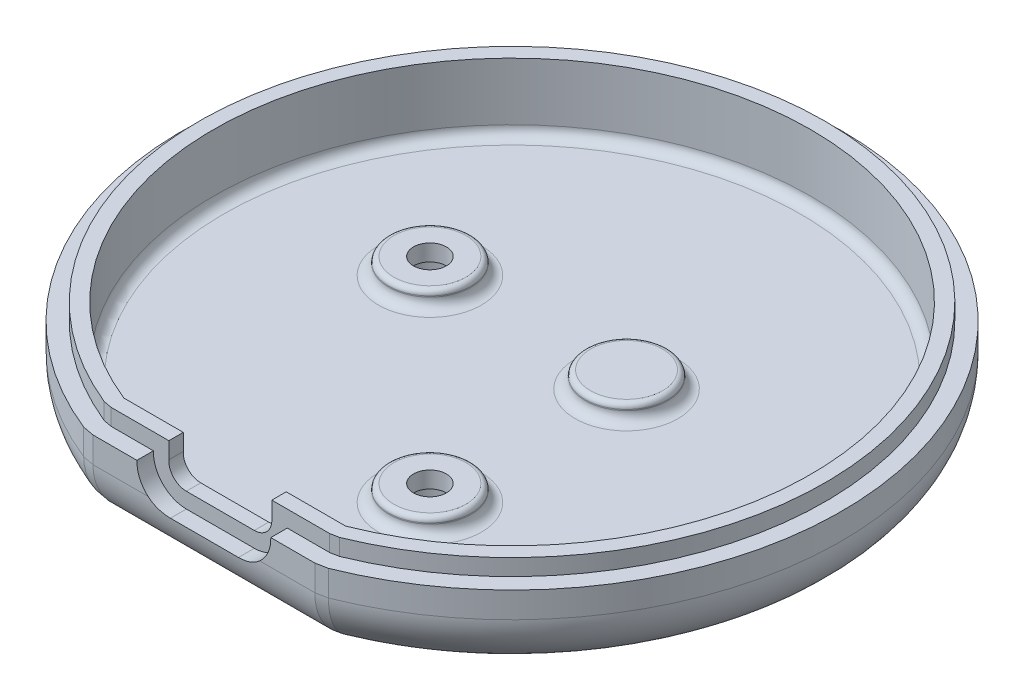
SolidWorks part; units mm, degrees
ref_plane "Front Plane" through (0, 0, 0) normal (0, 0, 1) x (1, 0, 0)
ref_plane "Top Plane" through (0, 0, 0) normal (0, 1, 0) x (1, 0, 0)
ref_plane "Right Plane" through (0, 0, 0) normal (1, 0, 0) x (0, 0, -1)
sketch "Sketch1" plane through (0, 0, 0) normal (0, 1, 0) x (1, 0, 0)
  line L0 (-10.7696, -29) -> (-11.8836, -28.7855)
  line L1 (25, -10.3553) -> (25, 10.3553)
  line L2 (25, 10.3553) -> (10.3553, 25)
  line L3 (10.3553, 25) -> (-10.3553, 25)
  line L4 (-10.3553, 25) -> (-25, 10.3553)
  line L5 (-25, 10.3553) -> (-25, -10.3553)
  line L6 (-25, -10.3553) -> (-10.3553, -25)
  line L7 (-10.3553, -25) -> (10.3553, -25)
  line L8 (10.3553, -25) -> (25, -10.3553)
  line L9 (10.7696, 26) -> (-10.7696, 26)
  line L10 (-10.7696, 26) -> (-26, 10.7696)
  line L11 (-26, 10.7696) -> (-26, -10.7696)
  line L12 (-26, -10.7696) -> (-10.7696, -26)
  line L13 (-10.7696, -26) -> (10.7696, -26)
  line L14 (10.7696, -26) -> (26, -10.7696)
  line L15 (26, -10.7696) -> (26, 10.7696)
  line L16 (26, 10.7696) -> (10.7696, 26)
  line L17 (-10.7696, -29) -> (10.7696, -29)
  line L18 (10.7696, -29) -> (11.8836, -28.7855)
  circle A0 centre (0, 0) radius 25 construction
  circle A1 centre (0, 0) radius 26 construction
  arc A2 (-10.7696, -26) -> (10.7696, -26) centre (0, 0.9261) cw
  arc A3 (-11.8836, -28.7855) -> (11.8836, -28.7855) centre (0, 0.9261) cw
  dimension "D3" = 29
  dimension "D1" = 50
  dimension "D2" = 1
  dimension "D4" = 3
  dimension "D5" = 3
extrude "Boss-Extrude1" add sketch "Sketch1" along normal blind 25 contours A3 L0 L17 L18 L13 A2 region at (-11.1582, 0, 28.0182)
sketch "Sketch2" plane through (0, 25, 0) normal (0, 1, 0) x (1, 0, 0)
  line L0 (10.7696, -29) -> (11.8836, -28.7855) construction
  line L1 (-10.7696, -29) -> (10.7696, -29) construction
  line L2 (-10.7696, -29) -> (-11.8836, -28.7855) construction
  line L3 (10.7696, -29) -> (11.8836, -28.7855)
  line L4 (-10.7696, -29) -> (10.7696, -29)
  line L5 (-10.7696, -29) -> (-11.8836, -28.7855)
  arc A0 (11.8836, -28.7855) -> (-11.8836, -28.7855) centre (0, 0.9261) ccw construction
  arc A1 (11.8836, -28.7855) -> (-11.8836, -28.7855) centre (0, 0.9261) ccw
extrude "Boss-Extrude2" add sketch "Sketch2" against normal blind 3
sketch "Sketch3" plane through (0, 0, 0) normal (0, -1, 0) x (1, 0, 0)
  line L0 (10.7696, 29) -> (11.8836, 28.7855) construction
  line L1 (-10.7696, 29) -> (10.7696, 29) construction
  line L2 (-10.7696, 29) -> (-11.8836, 28.7855) construction
  line L3 (10.7696, 29) -> (11.8836, 28.7855)
  line L4 (-10.7696, 29) -> (10.7696, 29)
  line L5 (-10.7696, 29) -> (-11.8836, 28.7855)
  arc A0 (-11.8836, 28.7855) -> (11.8836, 28.7855) centre (0, -0.9261) ccw construction
  arc A1 (-11.8836, 28.7855) -> (11.8836, 28.7855) centre (0, -0.9261) ccw
extrude "Boss-Extrude3" add sketch "Sketch3" against normal blind 3
sketch "Sketch5" plane through (0, 0, 29) normal (0, 0, 1) x (1, 0, 0)
  line L0 (0, 0) -> (0, 7.9) construction
  line L1 (-10.7696, 0) -> (10.7696, 0) construction
  line L2 (-3.3, 7.9) -> (3.3, 7.9) construction
  line L3 (-3.3, 9.6) -> (3.3, 9.6)
  line L4 (-3.3, 6.2) -> (3.3, 6.2)
  line L5 (-3.3, 11.1) -> (3.3, 11.1)
  line L6 (-3.3, 4.7) -> (3.3, 4.7)
  arc A0 (-3.3, 9.6) -> (-3.3, 6.2) centre (-3.3, 7.9) ccw
  arc A1 (3.3, 6.2) -> (3.3, 9.6) centre (3.3, 7.9) ccw
  arc A2 (3.3, 4.7) -> (3.3, 11.1) centre (3.3, 7.9) ccw
  arc A3 (-3.3, 11.1) -> (-3.3, 4.7) centre (-3.3, 7.9) ccw
  point P6 (0, 7.9)
  point P11 (-5, 7.9)
  point P12 (5, 7.9)
  dimension "D1" = 10
  dimension "D2" = 3.4
  dimension "D3" = 6.2
  dimension "D4" = 1.5
extrude "Cut-Extrude1" cut sketch "Sketch5" against normal blind 3 contours L4 A1 L3 A0 region at (0, 7.9, 29)
fillet "Fillet1" radius 5.5 4 edges at (0, 0, 29) (0, 0, -32.9261) (-11.3266, 0, 28.8927) (11.3266, 0, 28.8927)
fillet "Fillet2" radius 2 4 edges at (-11.3266, 25, 28.8927) (0, 25, -32.9261) (0, 25, 29) (11.3266, 25, 28.8927)
sketch "Sketch6" plane through (0, 3, 0) normal (0, 1, 0) x (1, 0, 0)
  line L0 (6.27, -13.32) -> (-12.8219, -13.32) construction
  line L1 (-12.8219, -13.32) -> (-12.8219, 5.7719) construction
  line L2 (10.7696, -26) -> (-10.7696, -26) construction
  line L3 (10.7696, -26) -> (-10.7696, -26)
  line L4 (6.27, -13.32) -> (6.27, 5.7719) construction
  line L5 (6.27, 5.7719) -> (-12.8219, 5.7719) construction
  circle A0 centre (-12.8219, 5.7719) radius 1.6
  circle A1 centre (6.27, -13.32) radius 1.6
  circle A2 centre (6.27, -13.32) radius 4
  circle A3 centre (-12.8219, 5.7719) radius 4
  circle A4 centre (6.27, 5.7719) radius 4
  point P9 (0, -26)
  dimension "D2" = 3.2
  dimension "D5" = 8
  dimension "D6" = 8
  dimension "D1" = 27
  dimension "D3" = 12.68
  dimension "D4" = 6.27
extrude "Boss-Extrude4" add sketch "Sketch6" along normal blind 1.6 contours A3 A0 | A4 | A2 A1 region at (2.3831, 3, 13.32) region at (-16.7087, 3, -5.7719) region at (6.27, 3, -5.7719)
fillet "Fillet3" radius 1 3 edges at (6.27, 3, 9.32) (6.27, 3, -9.7719) (-12.8219, 3, -9.7719)
fillet "Fillet4" radius 0.5 3 edges at (6.27, 4.6, 17.32) (6.27, 4.6, -1.7719) (-12.8219, 4.6, -1.7719)
sketch "Sketch7" plane through (0, 3, 0) normal (0, 1, 0) x (1, 0, 0)
  circle A0 centre (6.27, -13.32) radius 1.6 construction
  circle A1 centre (-12.8219, 5.7719) radius 1.6 construction
  circle A2 centre (6.27, -13.32) radius 1.6
  circle A3 centre (-12.8219, 5.7719) radius 1.6
extrude "Cut-Extrude2" cut sketch "Sketch7" against normal blind 3
fillet "Fillet5" radius 1 2 edges at (0, 3, 26) (0, 3, -29.9261)
sketch "Sketch8" plane through (0, 25, 0) normal (0, 1, 0) x (1, 0, 0)
  line L0 (11.8836, -28.7855) -> (10.7696, -29) construction
  line L1 (10.7696, -29) -> (-10.7696, -29) construction
  line L2 (-10.7696, -29) -> (-11.8836, -28.7855) construction
  line L3 (11.8836, -28.7855) -> (10.7696, -29)
  line L4 (-10.7696, -29) -> (-11.8836, -28.7855)
  line L5 (10.7696, -29) -> (-10.7696, -29)
  arc A0 (11.8836, -28.7855) -> (-11.8836, -28.7855) centre (0, 0.9261) ccw construction
  arc A1 (11.8836, -28.7855) -> (-11.8836, -28.7855) centre (0, 0.9261) ccw
extrude "Cut-Extrude3" cut sketch "Sketch8" against normal blind 17
sketch "Sketch9" plane through (0, 8, 0) normal (0, 1, 0) x (1, 0, 0)
  line L8 (-4.9971, -29) -> (-4.9971, -26)
  line L9 (-4.9971, -26) -> (-10.7696, -26)
  line L10 (10.7696, -26) -> (4.9971, -26)
  line L12 (4.9971, -29) -> (10.7696, -29)
  line L13 (10.7696, -29) -> (11.8836, -28.7855)
  line L14 (-11.8836, -28.7855) -> (-10.7696, -29)
  line L15 (-10.7696, -29) -> (-4.9971, -29)
  line L17 (-4.9971, -26) -> (-10.7696, -26)
  line L18 (10.7696, -26) -> (4.9971, -26)
  line L20 (4.9971, -29) -> (10.7696, -29)
  line L21 (10.7696, -29) -> (11.8836, -28.7855)
  line L22 (-11.8836, -28.7855) -> (-10.7696, -29)
  line L23 (-10.7696, -29) -> (-4.9971, -29)
  line L24 (-4.9971, -29) -> (-4.9971, -26)
  line L26 (4.9971, -26) -> (4.9971, -29)
  line L27 (4.9971, -26) -> (4.9971, -29)
  arc A2 (10.7696, -26) -> (-10.7696, -26) centre (0, 0.9261) ccw
  arc A3 (11.8836, -28.7855) -> (-11.8836, -28.7855) centre (0, 0.9261) ccw
  arc A4 (10.7696, -26) -> (-10.7696, -26) centre (0, 0.9261) ccw
  arc A5 (11.8836, -28.7855) -> (-11.8836, -28.7855) centre (0, 0.9261) ccw
  dimension "D1" = 0
extrude "Boss-Extrude5" add sketch "Sketch9" along normal blind 1.6 contours L24 L17 A4 L18 L27 L20 L21 A5 L22 L23
sketch "Sketch11" plane through (0, 9.6, 0) normal (0, 1, 0) x (1, 0, 0)
  line L0 (-11.8836, -28.7855) -> (-10.7696, -29) construction
  line L1 (10.7696, -29) -> (11.8836, -28.7855) construction
  line L2 (4.9971, -29) -> (10.7696, -29) construction
  line L3 (-10.7696, -29) -> (-4.9971, -29) construction
  line L4 (-11.8836, -28.7855) -> (-10.7696, -29)
  line L5 (10.7696, -29) -> (11.8836, -28.7855)
  line L6 (4.9971, -29) -> (10.7696, -29)
  line L7 (-10.7696, -29) -> (-4.9971, -29)
  line L8 (-5, -29) -> (-3.3, -29) construction
  line L9 (3.3, -29) -> (5, -29) construction
  line L10 (-3.3, -29) -> (3.3, -29) construction
  line L11 (3.3, -29) -> (5, -29)
  line L12 (-5, -29) -> (-3.3, -29)
  line L13 (-3.3, -29) -> (3.3, -29)
  line L14 (-5, -27.4) -> (-3.3, -27.4)
  line L15 (-3.3, -27.4) -> (3.3, -27.4)
  line L16 (3.3, -27.4) -> (5, -27.4)
  line L17 (4.9971, -27.4) -> (10.6169, -27.4)
  line L18 (10.6169, -27.4) -> (11.4293, -27.2436)
  line L19 (-11.4293, -27.2436) -> (-10.6169, -27.4)
  line L20 (-10.6169, -27.4) -> (-4.9971, -27.4)
  arc A0 (11.8836, -28.7855) -> (-11.8836, -28.7855) centre (0, 0.9261) ccw construction
  arc A1 (11.8836, -28.7855) -> (-11.8836, -28.7855) centre (0, 0.9261) ccw
  arc A2 (11.4293, -27.2436) -> (-11.4293, -27.2436) centre (0, 0.9261) ccw
  line M8 (-10.7696, -29) -> (-4.9971, -29)
  line M9 (-4.9971, -29) -> (-4.9971, -26)
  line M13 (4.9971, -26) -> (4.9971, -29)
  line M14 (4.9971, -29) -> (10.7696, -29)
  line M15 (10.7696, -29) -> (11.8836, -28.7855)
  arc M16 (11.8836, -28.7855) -> (-11.8836, -28.7855) centre (0, 0.9261) ccw
  line M17 (-11.8836, -28.7855) -> (-10.7696, -29)
  dimension "D1" = 1.6
extrude "Cut-Extrude4" cut sketch "Sketch11" against normal blind 1.6 contours A2 L18 L17 L16 L6 L7 L14 L20 L19 M13 M14 M15 M16 M17 M8 M9 region at (0, 9.6, -32.0356)
sketch "Sketch12" plane through (0, 0, 0) normal (0, -1, 0) x (1, 0, 0)
  circle A0 centre (6.27, 13.32) radius 1.6 construction
  circle A1 centre (-12.8219, -5.7719) radius 1.6 construction
  circle A2 centre (6.27, 13.32) radius 1.6
  circle A3 centre (-12.8219, -5.7719) radius 1.6
  circle A4 centre (-12.8219, -5.7719) radius 3.1
  circle A5 centre (6.27, 13.32) radius 3.1
  dimension "D1" = 1.5
extrude "Cut-Extrude5" cut sketch "Sketch12" against normal blind 3 contours A4 | A5
extrude "Cut-Extrude6" cut sketch "Sketch5<3>" against normal up to surface (1.6 mm away) up to face at (-7.807, 8.8, 27.4)
sketch "Sketch5<3>" plane through (0, 0, 29) normal (0, 0, 1) x (1, 0, 0) same geometry as "Sketch5"
